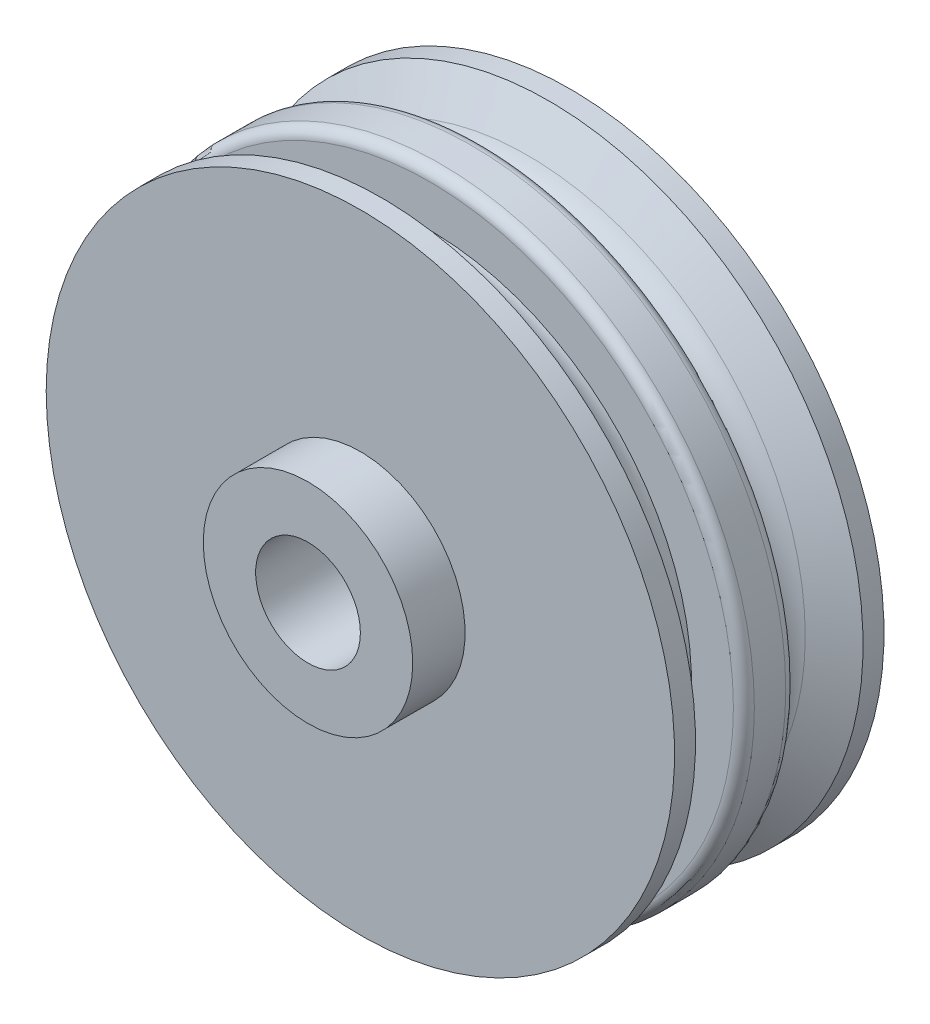
SolidWorks part; units mm, degrees
ref_plane "Front Plane" through (0, 0, 0) normal (0, 0, 1) x (1, 0, 0)
ref_plane "Top Plane" through (0, 0, 0) normal (0, 1, 0) x (1, 0, 0)
ref_plane "Right Plane" through (0, 0, 0) normal (1, 0, 0) x (0, 0, -1)
sketch "Sketch1" plane through (0, 0, 0) normal (0, 0, 1) x (1, 0, 0)
  circle A0 centre (0, 0) radius 5
  circle A1 centre (0, 0) radius 10
  dimension "D1" = 10
  dimension "D2" = 20
extrude "Boss-Extrude1" add sketch "Sketch1" along normal blind 30
sketch "Sketch4" plane through (0, 0, 0) normal (0, 1, 0) x (1, 0, 0)
  line L0 (10, 0) -> (10, -5)
  line L1 (10, -30) -> (10, 0) construction
  line L2 (10, -30) -> (10, -25)
  line L3 (10, -5) -> (30, -5)
  line L4 (10, -25) -> (30, -25)
  line L5 (30, -5) -> (30, -7)
  line L6 (25, -9.8868) -> (25, -20.1132)
  line L7 (30, -7) -> (25, -9.8868)
  line L8 (0, 0) -> (0, -30)
  line L9 (-10, -30) -> (10, -30) construction
  line L10 (10, -5) -> (10, -25)
  line L11 (30, -25) -> (30, -23)
  line L12 (30, -23) -> (25, -20.1132)
  dimension "D1" = 5
  dimension "D2" = 5
  dimension "D3" = 20
  dimension "D4" = 20
  dimension "D5" = 5
  dimension "D6" = 2
  dimension "D7" = 2
  dimension "D8" = 120
  dimension "D9" = 120
revolve "Revolve1" add sketch "Sketch4" angle 360 about L8 region at (18.4936, 0, 15)
fillet "Fillet1" radius 3 2 edges at (-25, 0, 20.1132) (-25, 0, 9.8868)
ref_plane "Plane1" through (0, 0, 18.3812) normal (0, 0, 1) x (1, 0, 0)
sketch "Sketch6" plane through (0, 0, 0) normal (0, 1, 0) x (1, 0, 0)
  line L0 (0, 1.5637) -> (0, -34.8722)
ref_axis "Axis1" through (0, 0, -1.5637) along (0, 0, 1)
sketch "Sketch5" plane through (0, 0, 18.3812) normal (0, 0, 1) x (1, 0, 0)
  circle A0 centre (0, 0) radius 30
  circle A1 centre (0, 0) radius 25
  dimension "D1" = 60
extrude "Boss-Extrude2" add sketch "Sketch5" against normal blind 5
fillet "Fillet2" radius 1 2 edges at (30, 0, 18.3812) (30, 0, 13.3812)
